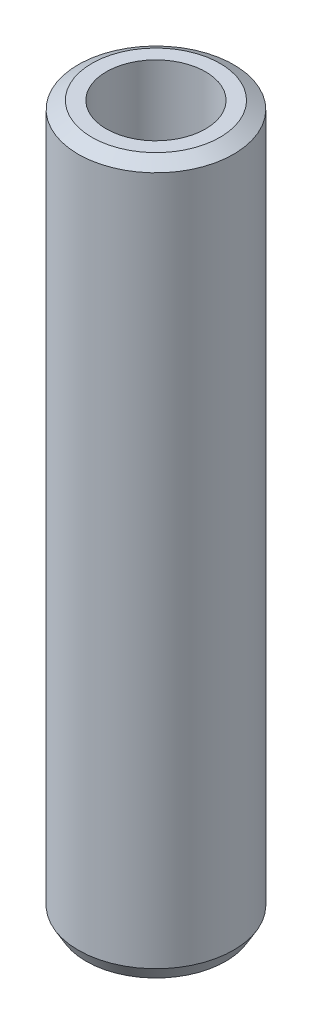
SolidWorks part; units mm, degrees
ref_plane "Front Plane" through (0, 0, 0) normal (0, 0, 1) x (1, 0, 0)
ref_plane "Top Plane" through (0, 0, 0) normal (0, 1, 0) x (1, 0, 0)
ref_plane "Right Plane" through (0, 0, 0) normal (1, 0, 0) x (0, 0, -1)
sketch "Sketch1" plane through (0, 0, 0) normal (0, 1, 0) x (1, 0, 0)
  circle A0 centre (0, 0) radius 52.5
  dimension "SHAFT_OD" = 105
extrude "Boss-Extrude1" add sketch "Sketch1" along normal blind 480.3488
sketch "Sketch2" plane through (0, 0, 0) normal (0, 1, 0) x (1, 0, 0)
  circle A0 centre (0, 0) radius 33.5167
  dimension "BORE_D" = 67.0333
extrude "Cut-Extrude1" cut sketch "Sketch2" along normal through all
chamfer "Chamfer1" distance 5.3121 angle 60 2 edges at (0, 480.3488, 52.5) (0, 0, 52.5) first distance on face at (0, 480.3488, 52.5) first distance on face at (0, 0, 33.5167)
